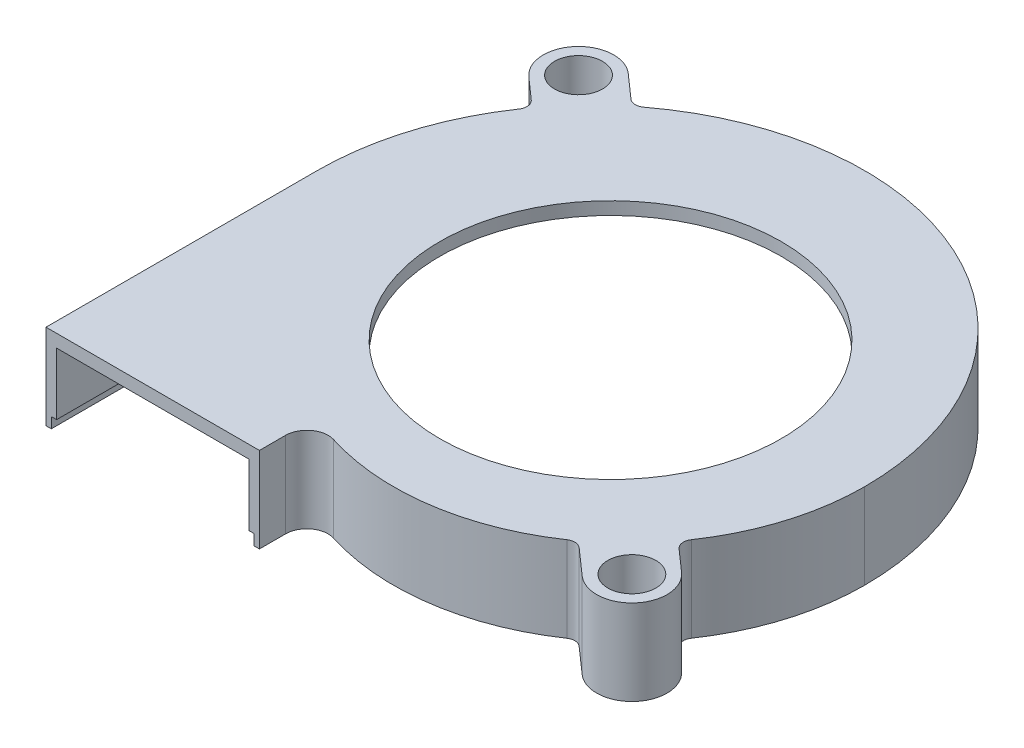
SolidWorks part; units mm, degrees
material "PET"
ref_plane "Спереди" through (0, 0, 0) normal (0, 0, 1) x (1, 0, 0)
ref_plane "Сверху" through (0, 0, 0) normal (0, 1, 0) x (1, 0, 0)
ref_plane "Справа" through (0, 0, 0) normal (1, 0, 0) x (0, 0, -1)
sketch "Эскиз1" plane through (0, 0, 0) normal (0, 1, 0) x (1, 0, 0)
  line L0 (0, -37.0288) -> (0, 52.769) construction
  line L1 (-41.2177, 0) -> (28.9689, 0) construction
  line L2 (-27.5, -25.4) -> (-7.5, -25.4)
  line L3 (-7.5, -25.4) -> (-7.5, -22.9558)
  line L4 (-27.5, -25.4) -> (-27.5, 0)
  line L5 (17.8147, -20.4728) -> (22.1853, -15.5272) construction
  line L6 (-25.1853, 17.5272) -> (-20.8147, 22.4728) construction
  line L7 (-23, 20) -> (20, -18) construction
  line L8 (-20.8147, 22.4728) -> (-18.5989, 20.5146)
  line L9 (-25.1853, 17.5272) -> (-23.2069, 15.7789)
  line L10 (17.8147, -20.4728) -> (15.377, -18.3185)
  line L11 (22.1853, -15.5272) -> (20.1437, -13.7231)
  circle A0 centre (0, 0) radius 16
  arc A1 (23.8, 0) -> (-17.3331, 20.4667) centre (-1.85, 0.0168) ccw
  circle A2 centre (-23, 20) radius 2.25
  circle A3 centre (20, -18) radius 2.25
  arc A4 (23.8, 0) -> (19.9791, -12.4113) centre (1.7319, 0) cw
  arc A5 (22.1853, -15.5272) -> (17.8147, -20.4728) centre (20, -18) cw
  arc A6 (-25.1853, 17.5272) -> (-20.8147, 22.4728) centre (-23, 20) cw
  arc A7 (14.152, -18.2412) -> (-4.899, -21.0483) centre (1.7319, 0) cw
  arc A8 (-23.0428, 14.4662) -> (-27.5, 0) centre (-1.85, 0.0168) ccw
  arc A9 (-4.899, -21.0483) -> (-7.5, -22.9558) centre (-5.5, -22.9558) ccw
  arc A10 (-18.5989, 20.5146) -> (-17.3331, 20.4667) centre (-17.9367, 21.2639) ccw
  arc A11 (-23.2069, 15.7789) -> (-23.0428, 14.4662) centre (-23.8691, 15.0296) cw
  arc A12 (20.1437, -13.7231) -> (19.9791, -12.4113) centre (20.8059, -12.9738) cw
  arc A13 (15.377, -18.3185) -> (14.152, -18.2412) centre (14.7148, -19.0678) ccw
  point P14 (0, 25.6)
  point P16 (16, 0)
  point P17 (0, -22)
  point P20 (23.8, 0)
  point P26 (0, -16)
  point P34 (-22.5346, 15.1848)
  point P41 (14.784, -17.7945)
  dimension "D1" = 18
  dimension "D2" = 20
  dimension "D8" = 51
  dimension "D11" = 3.3
  dimension "D12" = 7.8
  dimension "D13" = 6
  dimension "D14" = 2
  dimension "D5" = 4.5
  dimension "D6" = 32
  dimension "D15" = 1
  dimension "D3" = 23
  dimension "D4" = 20
  dimension "D7" = 51.3
  dimension "D9" = 20
  dimension "D10" = 25.4
extrude "Бобышка-Вытянуть1" add sketch "Эскиз1" against normal blind 8
sketch "Эскиз2" plane through (0, -8, 0) normal (0, -1, 0) x (-1, 0, 0)
  line L12 (7.5, -25.4) -> (7.5, -22.9558) construction
  line L13 (27.5, 0) -> (27.5, -25.4) construction
  line L14 (7.5, -25.4) -> (7.5, -22.9558) construction
  line L15 (27.5, 0) -> (27.5, -25.4) construction
  line L16 (8.5, -25.4) -> (8.5, -22.9558)
  line L17 (26.5, 0.0003) -> (26.5, -25.4)
  line L18 (26.5, -25.4) -> (8.5, -25.4)
  arc A19 (17.3331, 20.4667) -> (-23.8, 0) centre (1.85, 0.0168) ccw construction
  arc A20 (-23.8, 0) -> (-19.9791, -12.4113) centre (-1.7319, 0) ccw construction
  arc A21 (-14.152, -18.2412) -> (4.899, -21.0483) centre (-1.7319, 0) ccw construction
  arc A22 (7.5, -22.9558) -> (4.899, -21.0483) centre (5.5, -22.9558) ccw construction
  arc A23 (27.5, 0) -> (23.0428, 14.4662) centre (1.85, 0.0168) ccw construction
  arc A24 (17.3331, 20.4667) -> (-23.8, 0) centre (1.85, 0.0168) ccw construction
  arc A25 (-23.8, 0) -> (-19.9791, -12.4113) centre (-1.7319, 0) ccw construction
  arc A26 (-14.152, -18.2412) -> (4.899, -21.0483) centre (-1.7319, 0) ccw construction
  arc A27 (7.5, -22.9558) -> (4.899, -21.0483) centre (5.5, -22.9558) ccw construction
  arc A28 (27.5, 0) -> (23.0428, 14.4662) centre (1.85, 0.0168) ccw construction
  arc A29 (17.3331, 20.4667) -> (23.0428, 14.4662) centre (1.85, 0.0168) cw construction
  arc A30 (-19.9791, -12.4113) -> (-14.152, -18.2412) centre (-1.7319, 0) ccw construction
  arc A31 (8.5, -22.9558) -> (4.5986, -20.0945) centre (5.5, -22.9558) ccw
  arc A32 (-13.5892, -17.4146) -> (4.5986, -20.0945) centre (-1.7319, 0) ccw
  arc A33 (-19.1522, -11.8489) -> (-13.5892, -17.4146) centre (-1.7319, 0) ccw
  arc A34 (-22.8, 0.0003) -> (-19.1522, -11.8489) centre (-1.7319, 0) ccw
  arc A35 (16.7295, 19.6694) -> (-22.8, 0.0003) centre (1.85, 0.0168) ccw
  arc A36 (16.7295, 19.6694) -> (22.2166, 13.9029) centre (1.85, 0.0168) cw
  arc A37 (26.5, 0.0003) -> (22.2166, 13.9029) centre (1.85, 0.0168) ccw
  dimension "D1" = 1
extrude "Вырез-Вытянуть1" cut sketch "Эскиз2" against normal offset from surface (6.8 mm away) 1.2 up to face at (0, 0, 16)
sketch "Эскиз11" plane through (0, -8, 0) normal (0, -1, 0) x (1, 0, 0)
  line L0 (-8.5, 22.9558) -> (-8.5, 25.4) construction
  line L1 (-26.5, 25.4) -> (-26.5, -0.0003) construction
  line L2 (-8.5, 22.9558) -> (-8.5, 25.4)
  line L3 (-26.5, 25.4) -> (-26.5, -0.0003)
  line L4 (-27, 25.4) -> (-27, -0.0002)
  line L5 (-8, 22.9558) -> (-8, 25.4)
  line L6 (-27, 25.4) -> (-26.5, 25.4)
  line L7 (-8.5, 25.4) -> (-8, 25.4)
  arc A0 (-8.5, 22.9558) -> (-4.5986, 20.0945) centre (-5.5, 22.9558) ccw construction
  arc A1 (22.8, -0.0003) -> (-4.5986, 20.0945) centre (1.7319, 0) ccw construction
  arc A2 (-26.5, -0.0003) -> (22.8, -0.0003) centre (-1.85, -0.0168) ccw construction
  arc A3 (-8.5, 22.9558) -> (-4.5986, 20.0945) centre (-5.5, 22.9558) ccw
  arc A4 (22.8, -0.0003) -> (-4.5986, 20.0945) centre (1.7319, 0) ccw
  arc A5 (-26.5, -0.0003) -> (22.8, -0.0003) centre (-1.85, -0.0168) ccw
  arc A6 (-27, -0.0002) -> (23.3, -0.0001) centre (-1.85, -0.0168) ccw
  arc A7 (23.3, -0.0001) -> (-4.7488, 20.5714) centre (1.7319, 0) ccw
  arc A8 (-8, 22.9558) -> (-4.7488, 20.5714) centre (-5.5, 22.9558) ccw
  dimension "D1" = 0.5
extrude "Вырез-Вытянуть8" cut sketch "Эскиз11" against normal blind 1
